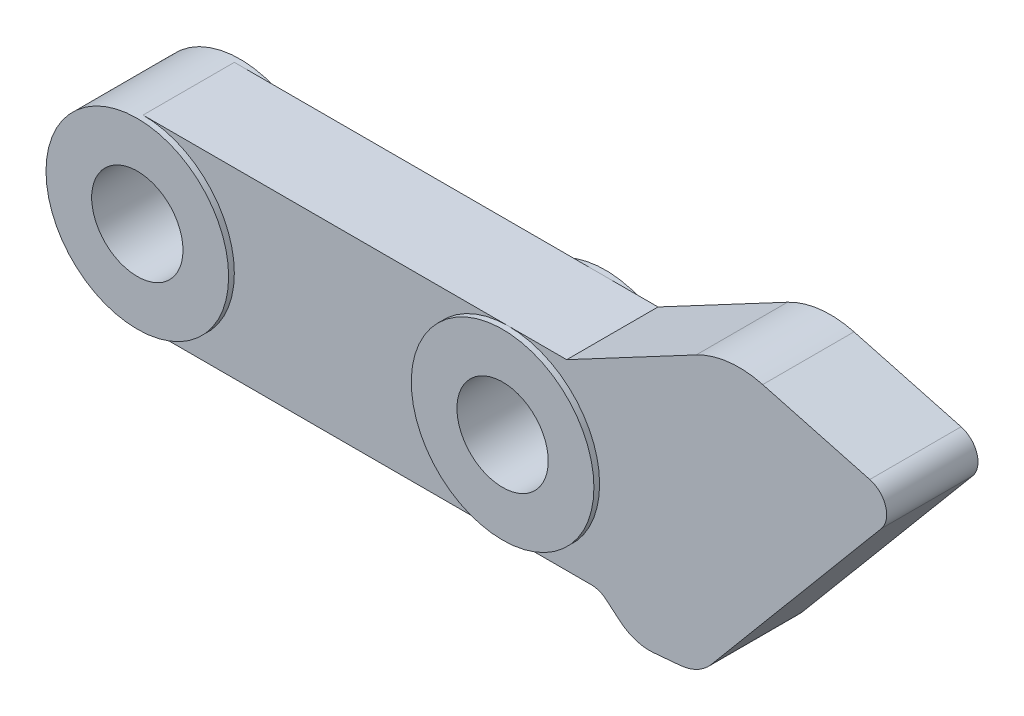
SolidWorks part; units mm, degrees
ref_plane "Front Plane" through (0, 0, 0) normal (0, 0, 1) x (1, 0, 0)
ref_plane "Top Plane" through (0, 0, 0) normal (0, 1, 0) x (1, 0, 0)
ref_plane "Right Plane" through (0, 0, 0) normal (1, 0, 0) x (0, 0, -1)
sketch "Sketch1" plane through (0, 0, 0) normal (0, 0, 1) x (1, 0, 0)
  line L0 (0, 0) -> (38.1, 0)
  line L1 (55, 0) -> (-55, 0) construction
  line L5 (35.8108, 12.7) -> (0, 12.7)
  line L6 (0, -55) -> (0, 55) construction
  line L7 (0, 12.7) -> (0, 0)
  line L8 (38.1, 0) -> (42.9644, -4.0817)
  line L9 (42.9644, -4.0817) -> (59.2912, 15.3758)
  line L10 (59.2912, 15.3758) -> (47.0239, 18.6628)
  line L11 (47.0239, 18.6628) -> (35.8108, 12.7)
  dimension "D1" = 12.7
  dimension "D2" = 38.1
  dimension "D3" = 140
  dimension "D4" = 6.35
  dimension "D5" = 25.4
  dimension "D6" = 12.7
  dimension "D7" = 65
  dimension "D8" = 12.7
extrude "Boss-Extrude1" add sketch "Sketch1" along normal blind 6.35
fillet "Fillet1" radius 6.35 3 edges at (47.0239, 18.6628, 3.175) (0, 0, 3.175) (0, 12.7, 3.175)
sketch "Sketch2" plane through (0, 0, 6.35) normal (0, 0, 1) x (1, 0, 0)
  circle A0 centre (6.35, 6.35) radius 3.175
  circle A1 centre (31.75, 6.35) radius 3.175
  dimension "D1" = 6.35
  dimension "D2" = 25.4
extrude "Cut-Extrude1" cut sketch "Sketch2" against normal up to surface (6.35 mm away) up to face at (31.1602, 8.7763, 0)
sketch "Sketch3" plane through (0, 0, 6.35) normal (0, 0, 1) x (1, 0, 0)
  circle A0 centre (31.75, 6.35) radius 6.35
  circle A1 centre (6.35, 6.35) radius 6.35
  circle A2 centre (6.35, 6.35) radius 3.175 construction
  circle A3 centre (6.35, 6.35) radius 3.175
  circle A4 centre (31.75, 6.35) radius 3.175 construction
  circle A5 centre (31.75, 6.35) radius 3.175
  dimension "D1" = 12.7
extrude "Boss-Extrude2" add sketch "Sketch3" along normal blind 0.3969
sketch "Sketch4" plane through (0, 0, 0) normal (0, 0, -1) x (-1, 0, 0)
  circle A0 centre (-31.75, 6.35) radius 6.35
  circle A1 centre (-6.35, 6.35) radius 6.35
  circle A2 centre (-6.35, 6.35) radius 3.175 construction
  circle A3 centre (-31.75, 6.35) radius 3.175 construction
  circle A4 centre (-6.35, 6.35) radius 3.175
  circle A5 centre (-31.75, 6.35) radius 3.175
  dimension "D1" = 12.7
extrude "Boss-Extrude3" add sketch "Sketch4" along normal blind 0.3969
fillet "Fillet2" radius 1.5875 2 edges at (59.2912, 15.3758, 3.175) (38.1, 0, 3.175)
chamfer "Chamfer1" distance 3.175 angle 45 1 edges at (42.9644, -4.0817, 3.175)
fillet "Fillet3" radius 3.175 2 edges at (40.5322, -2.0409, 3.175) (45.0052, -1.6495, 3.175)
